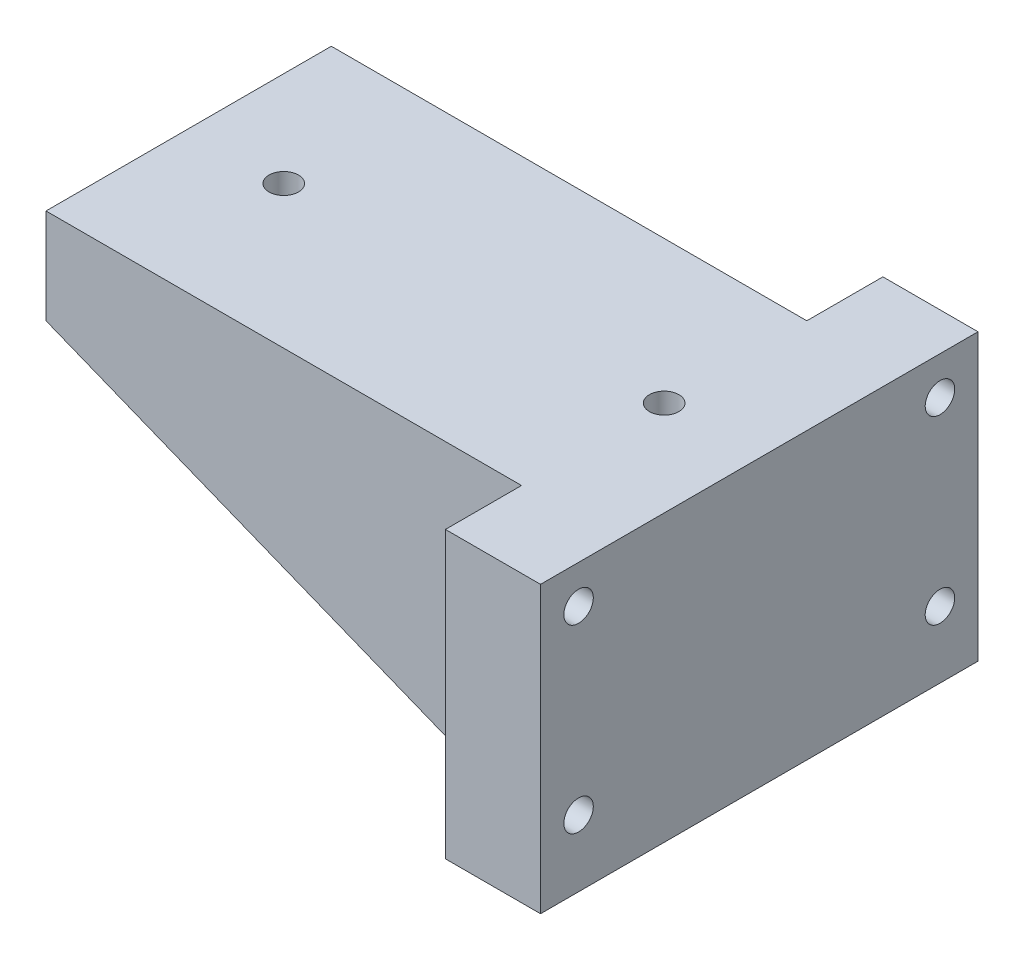
SolidWorks part; units mm, degrees
ref_plane "Front" through (0, 0, 0) normal (0, 0, 1) x (1, 0, 0)
ref_plane "Top" through (0, 0, 0) normal (0, 1, 0) x (1, 0, 0)
ref_plane "Right" through (0, 0, 0) normal (1, 0, 0) x (0, 0, -1)
sketch "Sketch1" plane through (0, 0, 0) normal (0, 1, 0) x (1, 0, 0)
  line L1 (-30, -15) -> (30, -15)
  line L2 (-30, -15) -> (-30, 15)
  line L3 (-30, 15) -> (30, 15)
  line L4 (30, -15) -> (30, 15)
  line L5 (-30, -15) -> (30, 15) construction
  line L6 (-30, 15) -> (30, -15) construction
  circle A0 centre (20, 0) radius 1.55
  circle A1 centre (-20, 0) radius 1.55
  point P0 (0, 0)
  dimension "D3" = 3.1
  dimension "D4" = 3.1
  dimension "D5" = 40
  dimension "D6" = 10
  dimension "D1" = 30
  dimension "D2" = 60
extrude "Boss-Extrude1" add sketch "Sketch1" along normal blind 10
sketch "Sketch2" plane through (30, 0, 0) normal (1, 0, 0) x (0, 0, -1)
  line L0 (-15, 10) -> (15, 10) construction
  line L1 (-23, 10) -> (23, 10)
  line L2 (-23, 10) -> (-23, -20)
  line L3 (-23, -20) -> (23, -20)
  line L4 (23, 10) -> (23, -20)
  line L5 (-23, 10) -> (23, -20) construction
  line L6 (-23, -20) -> (23, 10) construction
  line L7 (-15, 10) -> (-15, 0) construction
  line L8 (15, 10) -> (15, 0) construction
  line L9 (-15, 0) -> (15, 0) construction
  line L10 (-5, 0) -> (5, 0)
  line L11 (-5, 0) -> (-5, -20)
  line L12 (-5, -20) -> (5, -20)
  line L13 (5, 0) -> (5, -20)
  line L14 (-5, 0) -> (5, -20) construction
  line L15 (-5, -20) -> (5, 0) construction
  circle A0 centre (-19, 6) radius 1.55
  circle A1 centre (19, 6) radius 1.55
  circle A2 centre (-19, -13) radius 1.55
  circle A3 centre (19, -13) radius 1.55
  point P4 (0, -5)
  point P25 (0, -10)
  line M9 (-15, 0) -> (15, 0)
  line M10 (15, 0) -> (15, 10)
  line M12 (-15, 10) -> (-15, 0)
  dimension "D4" = 3.1
  dimension "D5" = 3.1
  dimension "D6" = 4
  dimension "D7" = 4
  dimension "D8" = 4
  dimension "D9" = 3.1
  dimension "D10" = 3.1
  dimension "D12" = 4
  dimension "D13" = 7
  dimension "D1" = 8
  dimension "D2" = 8
  dimension "D3" = 30
  dimension "D11" = 4
  dimension "D14" = 10
extrude "Boss-Extrude3" add sketch "Sketch2" against normal blind 10 contours L11 L1 L2 L3 A2 A0 M9 M12 | L13 L3 L4 L1 A3 A1 M9 M10 region at (30, -7.4068, 14.7638) region at (30, -7.4068, -14.7638)
extrude "Boss-Extrude4" add sketch "Sketch2<3>" against normal blind 6 contours L13 L11 L3 M9 region at (30, -10, 0)
sketch "Sketch2<3>" plane through (30, 0, 0) normal (1, 0, 0) x (0, 0, -1) same geometry as "Sketch2"
sketch "Sketch5" plane through (0, 0, -15) normal (0, 0, -1) x (-1, 0, 0)
  line L0 (-20, -20) -> (30, 0)
  line L1 (-20, 0) -> (30, 0) construction
  line L2 (-20, -20) -> (-20, 0)
  line L3 (-20, 0) -> (30, 0)
extrude "Boss-Extrude5" add sketch "Sketch5" against normal blind 6
sketch "Sketch6" plane through (0, 0, 15) normal (0, 0, 1) x (1, 0, 0)
  line L3 (20, -20) -> (20, 0)
  line L4 (20, 0) -> (-30, 0)
  line L5 (-30, 0) -> (20, -20)
  line L6 (20, -20) -> (20, 0)
  line L7 (20, 0) -> (-30, 0)
  line L8 (-30, 0) -> (20, -20)
  dimension "D1" = 0
extrude "Boss-Extrude6" add sketch "Sketch6" against normal blind 6
